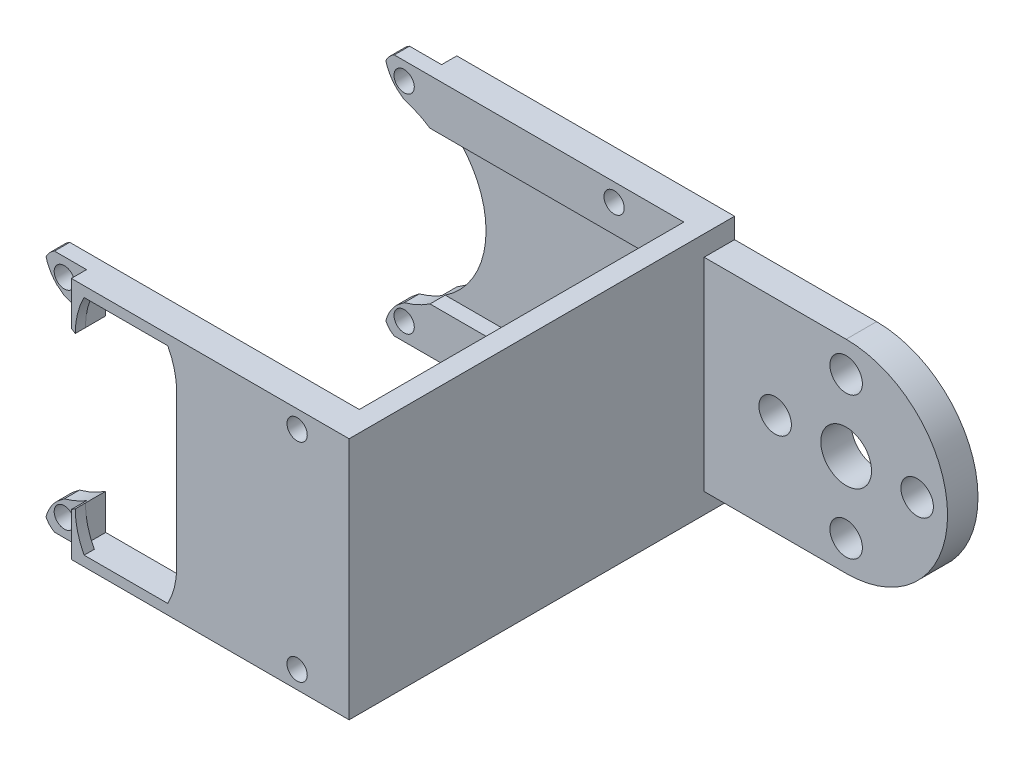
SolidWorks part; units mm, degrees
ref_plane "前视基准面" through (0, 0, 0) normal (0, 0, 1) x (1, 0, 0)
ref_plane "上视基准面" through (0, 0, 0) normal (0, 1, 0) x (1, 0, 0)
ref_plane "右视基准面" through (0, 0, 0) normal (1, 0, 0) x (0, 0, -1)
other "Configuration Table"
sketch "草图1" plane through (0, 0, 0) normal (0, 0, 1) x (1, 0, 0)
  line L1 (0, 0) -> (58, 0)
  line L2 (0, 0) -> (0, 24)
  line L3 (0, 24) -> (58, 24)
  line L4 (58, 0) -> (58, 24)
  dimension "D1" = 58
  dimension "D2" = 24
extrude "凸台-拉伸1" add sketch "草图1" along normal blind 3
sketch "草图2" plane through (0, 0, 3) normal (0, 0, 1) x (1, 0, 0)
  line L0 (58, 24) -> (0, 24) construction
  line L1 (30, 24) -> (32, 24)
  line L2 (30, 24) -> (30, 0)
  line L3 (30, 0) -> (32, 0)
  line L4 (32, 24) -> (32, 0)
  line L5 (0, 0) -> (58, 0) construction
  line L6 (0, 24) -> (0, 0) construction
  dimension "D1" = 30
  dimension "D2" = 2
extrude "凸台-拉伸2" add sketch "草图2" along normal blind 32
sketch "草图3" plane through (32, 0, 0) normal (1, 0, 0) x (0, 0, -1)
  line L1 (-35, 24) -> (-38, 24)
  line L2 (-35, 24) -> (-35, 0)
  line L3 (-35, 0) -> (-38, 0)
  line L4 (-38, 24) -> (-38, 0)
  dimension "D1" = 3
extrude "凸台-拉伸3" add sketch "草图3" against normal up to surface (32 mm away) up to face at (0, 12, 1.5)
sketch "草图4" plane through (0, 0, 0) normal (0, 0, -1) x (-1, 0, 0)
  line L0 (0, 24) -> (0, 0) construction
  circle A0 centre (0, 12) radius 9
  dimension "D1" = 18
extrude "切除-拉伸1" cut sketch "草图4" against normal through all
sketch "草图5" plane through (0, 0, 0) normal (0, 0, -1) x (-1, 0, 0)
  line L0 (-55, 12) -> (49945, 12) construction
  line L1 (-58, 0) -> (-58, 24) construction
  line L2 (0, 24) -> (0, 21) construction
  line L3 (-23.1237, 22.25) -> (-2.4237, 22.25) construction
  line L4 (-23.1237, 22.25) -> (-23.1237, 1.75) construction
  line L5 (-23.1237, 1.75) -> (-2.4237, 1.75) construction
  line L6 (-2.4237, 22.25) -> (-2.4237, 1.75) construction
  circle A0 centre (-2.4237, 22.25) radius 1
  circle A1 centre (-2.4237, 1.75) radius 1
  circle A2 centre (-23.1237, 1.75) radius 1
  circle A3 centre (-23.1237, 22.25) radius 1
  point P4 (-58, 12)
  point P9 (-2.4237, 12)
  dimension "D2" = 2
  dimension "D3" = 2
  dimension "D4" = 2
  dimension "D5" = 2
  dimension "D1" = 20.5
  dimension "D6" = 20.7
extrude "切除-拉伸2" cut sketch "草图5" against normal up to next
sketch "草图6" plane through (0, 0, 38) normal (0, 0, 1) x (1, 0, 0)
  line L0 (32, 12) -> (-49968, 12) construction
  line L1 (32, 24) -> (32, 0) construction
  line L2 (0, 0) -> (0, 3) construction
  line L3 (15, 23) -> (5, 23)
  line L4 (15, 23) -> (15, 1)
  line L5 (15, 1) -> (5, 1)
  line L6 (5, 23) -> (5, 1)
  point P4 (32, 12)
  point P10 (15, 12)
  dimension "D1" = 22
  dimension "D2" = 5
  dimension "D3" = 10
extrude "切除-拉伸3" cut sketch "草图6" against normal up to next
sketch "草图7" plane through (15, 0, 0) normal (-1, 0, 0) x (0, 0, 1)
  line L0 (37, 23) -> (37, 1)
  line L4 (35, 1) -> (38, 1)
  line L5 (38, 1) -> (38, 23)
  line L6 (38, 23) -> (35, 23)
  line L7 (35, 23) -> (35, 1)
  line L8 (35, 1) -> (38, 1)
  line L9 (38, 1) -> (38, 23)
  line L10 (38, 23) -> (35, 23)
  line L11 (35, 23) -> (35, 1)
  line M6 (35, 1) -> (38, 1)
  line M8 (38, 23) -> (35, 23)
  line M9 (35, 23) -> (35, 1)
  dimension "D2" = 1
  dimension "D1" = 0
extrude "切除-拉伸4" cut sketch "草图7" against normal blind 6 contours L0 M8 M9 M6 region at (15, 12, 36)
sketch "草图8" plane through (0, 0, 38) normal (0, 0, 1) x (1, 0, 0)
  line L1 (2.4237, 22.25) -> (26.8737, 22.25) construction
  line L2 (2.4237, 22.25) -> (2.4237, 1.75) construction
  line L3 (2.4237, 1.75) -> (26.8737, 1.75) construction
  line L4 (26.8737, 22.25) -> (26.8737, 1.75) construction
  circle A0 centre (2.4237, 22.25) radius 1 construction
  circle A1 centre (2.4237, 1.75) radius 1 construction
  circle A2 centre (2.4237, 22.25) radius 1
  circle A3 centre (2.4237, 1.75) radius 1
  circle A4 centre (26.8737, 22.25) radius 1
  circle A5 centre (26.8737, 1.75) radius 1
  dimension "D1" = 2
  dimension "D2" = 2
  dimension "D3" = 24.45
extrude "切除-拉伸5" cut sketch "草图8" against normal up to next
sketch "草图9" plane through (0, 0, 38) normal (0, 0, 1) x (1, 0, 0)
  line L0 (32, 12) -> (-49968, 12) construction
  line L1 (32, 24) -> (32, 0) construction
  line L2 (5, 23) -> (5, 19.4833) construction
  line L3 (5, 1) -> (5.8756, 1)
  line L4 (5, 4.5167) -> (5, 1)
  line L5 (10, 23) -> (10, -49977) construction
  line L6 (15, 23) -> (5, 23) construction
  line L7 (15, 23) -> (14.1244, 23)
  line L8 (15, 19.4833) -> (15, 23)
  line L9 (15, 4.5167) -> (15, 1)
  line L10 (15, 1) -> (14.1244, 1)
  line L13 (5, 19.4833) -> (5, 23)
  line L14 (5, 23) -> (15, 23)
  line L15 (15, 23) -> (15, 1)
  line L16 (15, 1) -> (5, 1)
  line L17 (5, 1) -> (5, 4.5167)
  line L18 (0, 3) -> (0, 0)
  line L19 (0, 0) -> (32, 0)
  line L20 (32, 0) -> (32, 24)
  line L21 (32, 24) -> (0, 24)
  line L22 (0, 24) -> (0, 21)
  line L23 (5, 19.4833) -> (5, 23)
  line L24 (5, 23) -> (5.8756, 23)
  arc A0 (5.8756, 23) -> (5, 19.4833) centre (12.5, 19.4833) ccw
  arc A1 (5.8756, 1) -> (5, 4.5167) centre (12.5, 4.5167) cw
  arc A2 (14.1244, 1) -> (15, 4.5167) centre (7.5, 4.5167) ccw
  arc A3 (0, 3) -> (5, 4.5167) centre (0, 12) ccw
  arc A4 (5, 19.4833) -> (0, 21) centre (0, 12) ccw
  arc A7 (14.1244, 23) -> (15, 19.4833) centre (7.5, 19.4833) cw
  point P4 (32, 12)
  point P9 (5, 19.4833)
  point P25 (5, 4.5167)
  point P34 (10, 23)
  point P39 (15, 4.5167)
  point P40 (15, 19.4833)
  dimension "D1" = 15
  dimension "D2" = 0
extrude "凸台-拉伸4" add sketch "草图9" against normal up to surface (1 mm away) up to face at (18, 12, 37)
sketch "草图11" plane through (0, 0, 0) normal (0, 0, -1) x (-1, 0, 0)
  line L5 (0, 21) -> (0, 24)
  line L6 (0, 24) -> (-58, 24)
  line L7 (-58, 24) -> (-58, 0)
  line L8 (-58, 0) -> (0, 0)
  line L9 (0, 0) -> (0, 3)
  line L10 (0, 21) -> (0, 24)
  line L11 (0, 24) -> (-1.4554, 24)
  line L13 (-1.4554, 0) -> (0, 0)
  line L14 (0, 0) -> (0, 3)
  circle A0 centre (-2.4237, 1.75) radius 1 construction
  circle A1 centre (-2.4237, 22.25) radius 1 construction
  circle A2 centre (-2.4237, 1.75) radius 1 construction
  circle A3 centre (-2.4237, 22.25) radius 1 construction
  arc A4 (-0.8996, 20.9549) -> (-1.4554, 24) centre (-2.4237, 22.25) ccw
  arc A5 (-1.4554, 0) -> (-0.8996, 3.0451) centre (-2.4237, 1.75) ccw
  arc A6 (-0.8996, 3.0451) -> (0, 3) centre (0, 12) ccw
  arc A7 (0, 21) -> (0, 3) centre (0, 12) ccw
  arc A8 (0, 21) -> (-0.8996, 20.9549) centre (0, 12) ccw
  circle A9 centre (-2.4237, 22.25) radius 2 construction
  circle A10 centre (-2.4237, 1.75) radius 2 construction
  dimension "D1" = 1
  dimension "D2" = 0
extrude "切除-拉伸6" cut sketch "草图11" against normal through all
sketch "草图12" plane through (0, 0, 0) normal (0, 0, -1) x (-1, 0, 0)
  line L0 (-0.4237, 22.25) -> (-2.4237, 20.6675)
  line L1 (-0.4237, 1.75) -> (-2.4237, 3.3325)
  line L4 (-1.4554, 24) -> (-58, 24)
  line L5 (-58, 24) -> (-58, 0)
  line L6 (-58, 0) -> (-1.4554, 0)
  line L7 (-1.4554, 24) -> (-58, 24)
  line L8 (-58, 24) -> (-58, 0)
  line L9 (-58, 0) -> (-1.4554, 0)
  arc A0 (-0.8996, 20.9549) -> (-1.4554, 24) centre (-2.4237, 22.25) ccw construction
  arc A1 (-0.8996, 20.9549) -> (-0.8996, 3.0451) centre (0, 12) ccw construction
  arc A5 (-1.4554, 0) -> (-0.8996, 3.0451) centre (-2.4237, 1.75) ccw
  arc A6 (-0.8996, 20.9549) -> (-0.8996, 3.0451) centre (0, 12) ccw
  arc A7 (-0.8996, 20.9549) -> (-1.4554, 24) centre (-2.4237, 22.25) ccw
  arc A8 (-1.4554, 0) -> (-0.8996, 3.0451) centre (-2.4237, 1.75) ccw
  arc A9 (-0.8996, 20.9549) -> (-0.8996, 3.0451) centre (0, 12) ccw
  arc A10 (-0.8996, 20.9549) -> (-1.4554, 24) centre (-2.4237, 22.25) ccw
  arc M7 (-1.4554, 0) -> (-0.8996, 3.0451) centre (-2.4237, 1.75) ccw
  arc M8 (-0.8996, 3.0451) -> (-0.8996, 20.9549) centre (0, 12) cw
  arc M9 (-0.8996, 20.9549) -> (-1.4554, 24) centre (-2.4237, 22.25) ccw
  dimension "D1" = 0
extrude "切除-拉伸7" cut sketch "草图12" against normal through all contours L1 M7 M8 | L0 M9 M8 region at (1.1624, 21.3406, 0) region at (1.1624, 2.6594, 0)
sketch "草图13" plane through (0, 0, 0) normal (0, 0, -1) x (-1, 0, 0)
  line L1 (-55, 12) -> (49945, 12) construction
  line L6 (-0.4237, 1.75) -> (-2.4237, 3.3325)
  line L7 (-2.4237, 20.6675) -> (-0.4237, 22.25)
  line L8 (-1.4554, 24) -> (-58, 24)
  line L9 (-58, 24) -> (-58, 0)
  line L10 (-58, 0) -> (-1.4554, 0)
  line L11 (-0.4237, 1.75) -> (-2.4237, 3.3325)
  line L12 (-2.4237, 20.6675) -> (-0.4237, 22.25)
  line L13 (-1.4554, 24) -> (-58, 24)
  line L14 (-58, 24) -> (-58, 0)
  line L15 (-58, 0) -> (-1.4554, 0)
  circle A0 centre (-4.6247, -0.1868) radius 4.1508
  circle A1 centre (-4.6247, 24.1868) radius 4.1508
  arc A4 (-1.4554, 0) -> (-0.4237, 1.75) centre (-2.4237, 1.75) ccw
  arc A5 (-2.4237, 20.6675) -> (-2.4237, 3.3325) centre (0, 12) ccw
  arc A6 (-0.4237, 22.25) -> (-1.4554, 24) centre (-2.4237, 22.25) ccw
  arc A7 (-1.4554, 0) -> (-0.4237, 1.75) centre (-2.4237, 1.75) ccw
  arc A8 (-2.4237, 20.6675) -> (-2.4237, 3.3325) centre (0, 12) ccw
  arc A9 (-0.4237, 22.25) -> (-1.4554, 24) centre (-2.4237, 22.25) ccw
  point P18 (-58, 12)
  point P20 (0, 0)
  arc M15 (-1.4554, 0) -> (-0.4237, 1.75) centre (-2.4237, 1.75) ccw
  line M16 (-0.4237, 1.75) -> (-2.4237, 3.3325)
  arc M19 (-0.4237, 22.25) -> (-1.4554, 24) centre (-2.4237, 22.25) ccw
  dimension "D1" = 0
sketch "草图14" plane through (0, 0, 0) normal (0, 0, -1) x (-1, 0, 0)
extrude "切除-拉伸8" cut sketch "草图13" against normal through all contours A1 L12 M19 | A0 M15 M16 region at (0.8027, 1.7481, 0) region at (0.8027, 22.2519, 0)
sketch "草图15" plane through (0, 24, 0) normal (0, 1, 0) x (1, 0, 0)
  line L0 (1.4554, -38) -> (32, -38) construction
  line L1 (4.6167, -38) -> (-5.8127, -38)
  line L2 (4.6167, -38) -> (4.6167, -36.5)
  line L3 (4.6167, -36.5) -> (-5.8127, -36.5)
  line L4 (-5.8127, -38) -> (-5.8127, -36.5)
  line L5 (0.6167, -38) -> (0.6167, -35) construction
  line L6 (30, -19) -> (-49970, -19) construction
  line L7 (30, -35) -> (30, -3) construction
  line L8 (4.6167, -1.5) -> (-5.8127, -1.5)
  line L9 (-5.8127, 0) -> (-5.8127, -1.5)
  line L10 (4.6167, 0) -> (-5.8127, 0)
  line L11 (4.6167, 0) -> (4.6167, -1.5)
  point P12 (30, -19)
  dimension "D1" = 1.5
  dimension "D2" = 4
extrude "切除-拉伸9" cut sketch "草图15" against normal through all
ref_axis "基准轴1" through (2.4237, 1.75, 3) along (0, 0, -1)
ref_axis "基准轴2" through (2.4237, 22.25, 3) along (0, 0, -1)
ref_plane "基准面1" through (2.4237, 0, 0) normal (-1, 0, 0) x (0, 0, 1)
sketch "草图16" plane through (2.4237, 0, 0) normal (-1, 0, 0) x (0, 0, 1)
  line L0 (38, 12) -> (-49962, 12) construction
  line L1 (38, 4.5167) -> (38, 19.4833) construction
  line L2 (3, 21.25) -> (3, 23.25) construction
  line L3 (1.5, 19.5) -> (3, 19.5)
  line L4 (1.5, 19.5) -> (1.5, 4.5)
  line L5 (1.5, 4.5) -> (3, 4.5)
  line L6 (3, 19.5) -> (3, 4.5)
  point P4 (38, 12)
  point P9 (3, 12)
  dimension "D1" = 1.5
  dimension "D2" = 15
extrude "切除-拉伸10" cut sketch "草图16" against normal up to surface (27.5763 mm away) up to face at (30, 12, 19)
sketch "草图17" plane through (0, 0, 3) normal (0, 0, 1) x (1, 0, 0)
  line L0 (55, 12) -> (-49945, 12) construction
  line L1 (58, 0) -> (58, 24) construction
  line L2 (46, 12) -> (46, 50012) construction
  circle A2 centre (46, 12) radius 7 construction
  circle A3 centre (53, 12) radius 1.6
  circle A4 centre (46, 12) radius 2.5
  circle A5 centre (46, 19) radius 1.6
  circle A6 centre (46, 5) radius 1.6
  circle A7 centre (39, 12) radius 1.6
  point P4 (58, 12)
  dimension "D1" = 14
  dimension "D2" = 3.2
  dimension "D3" = 5
  dimension "D5" = 3.2
  dimension "D6" = 3.2
  dimension "D7" = 3.2
  dimension "D4" = 12
extrude "切除-拉伸11" cut sketch "草图17" against normal up to next
sketch "草图18" plane through (0, 0, 0) normal (0, 0, -1) x (-1, 0, 0)
  line L0 (-46, 2) -> (-32, 2)
  line L1 (-32, 2) -> (-32, 0)
  line L2 (-4.6167, 0) -> (-58, 0) construction
  line L3 (-58, 12) -> (49942, 12) construction
  line L5 (-32, 0) -> (-32, 24) construction
  line L6 (-46, 22) -> (-32, 22)
  line L7 (-32, 22) -> (-32, 24)
  line L8 (-4.6167, 19.7257) -> (-4.6167, 24)
  line L9 (-4.6167, 24) -> (-58, 24)
  line L10 (-58, 24) -> (-58, 0)
  line L11 (-58, 0) -> (-4.6167, 0)
  line L12 (-4.6167, 0) -> (-4.6167, 4.2743)
  line L13 (-4.6167, 19.7257) -> (-4.6167, 24)
  line L14 (-4.6167, 24) -> (-58, 24)
  line L15 (-58, 24) -> (-58, 0)
  line L16 (-58, 0) -> (-4.6167, 0)
  line L17 (-4.6167, 0) -> (-4.6167, 4.2743)
  circle A0 centre (-46, 12) radius 10
  arc A2 (-4.6167, 19.7257) -> (-4.6167, 4.2743) centre (0, 12) ccw
  arc A3 (-4.6167, 19.7257) -> (-4.6167, 4.2743) centre (0, 12) ccw
  point P23 (-58, 12)
  line M17 (-4.6167, 24) -> (-58, 24)
  line M18 (-58, 24) -> (-58, 0)
  line M19 (-58, 0) -> (-4.6167, 0)
  dimension "D1" = 20
  dimension "D2" = 0
extrude "切除-拉伸12" cut sketch "草图18" against normal up to next contours L3 L15 L1 L0 A0 M19 | L3 A0 L6 L7 M18 M17 region at (39, 1.7136, 0) region at (57, 12.2864, 0)
